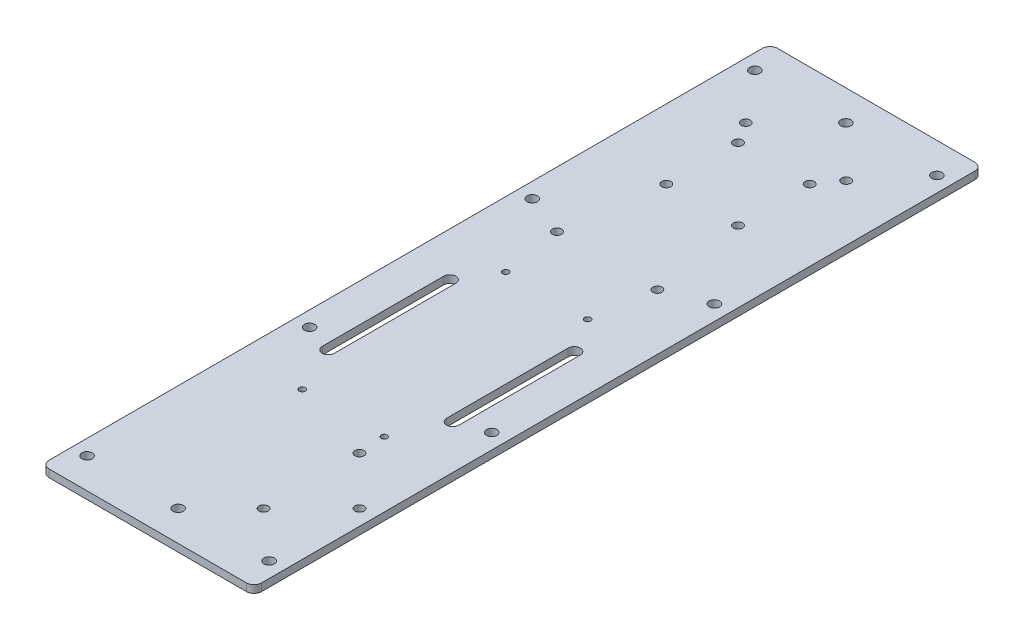
SolidWorks part; units mm, degrees
ref_plane "Front Plane" through (0, 0, 0) normal (0, 0, 1) x (1, 0, 0)
ref_plane "Top Plane" through (0, 0, 0) normal (0, 1, 0) x (1, 0, 0)
ref_plane "Right Plane" through (0, 0, 0) normal (1, 0, 0) x (0, 0, -1)
sketch "Sketch2" plane through (0, 0, 0) normal (0, 1, 0) x (1, 0, 0)
  line L0 (-44.45, 0) -> (44.45, 0) construction
  line L1 (-41.275, 152.4) -> (41.275, 152.4)
  line L2 (-44.45, 149.225) -> (-44.45, -149.225)
  line L3 (-41.275, -152.4) -> (41.275, -152.4)
  line L4 (44.45, 149.225) -> (44.45, -149.225)
  line L5 (0, 152.4) -> (0, -152.4) construction
  arc A0 (-44.45, -149.225) -> (-41.275, -152.4) centre (-41.275, -149.225) ccw
  arc A1 (41.275, -152.4) -> (44.45, -149.225) centre (41.275, -149.225) ccw
  arc A2 (41.275, 152.4) -> (44.45, 149.225) centre (41.275, 149.225) cw
  arc A3 (-41.275, 152.4) -> (-44.45, 149.225) centre (-41.275, 149.225) ccw
  point P8 (0, 0)
  point P13 (-44.45, -152.4)
  point P16 (44.45, -152.4)
  point P21 (-44.45, 152.4)
  dimension "D3" = 3.175
  dimension "D1" = 304.8
  dimension "D2" = 88.9
extrude "Plate Thickness" add sketch "Sketch2" along normal blind 3.175 contours L2 A0 L3 A1 L4 A2 L1 A3
sketch "Sketch3" plane through (0, 3.175, 0) normal (0, 1, 0) x (1, 0, 0)
  line L0 (-44.45, 149.225) -> (-44.45, -149.225) construction
  line L1 (-41.275, 152.4) -> (41.275, 152.4) construction
  line L4 (0, 152.4) -> (0, -152.4) construction
  line L5 (-41.275, -152.4) -> (41.275, -152.4) construction
  line L6 (-41.275, -152.4) -> (41.275, -152.4) construction
  circle A0 centre (-38.1, 139.7) radius 2.159
  circle A1 centre (-38.1, 46.5667) radius 2.159
  circle A2 centre (-38.1, -46.5667) radius 2.159
  circle A3 centre (-38.1, -139.7) radius 2.159
  circle A4 centre (38.1, -139.7) radius 2.159
  circle A5 centre (38.1, -46.5667) radius 2.159
  circle A6 centre (38.1, 46.5667) radius 2.159
  circle A7 centre (38.1, 139.7) radius 2.159
  circle A8 centre (0, 139.7) radius 2.159
  circle A9 centre (0, -139.7) radius 2.159
  point P6 (0, 0)
  point P37 (0, 0)
  dimension "D1" = 4.318
  dimension "D4" = 4.318
  dimension "D2" = 6.35
  dimension "D3" = 12.7
  dimension "D5" = 12.7
  dimension "D6" = 12.7
  dimension "D7" = 93.1333
  dimension "D8" = 93.1333
extrude "Mounting holes" cut sketch "Sketch3" against normal through all
sketch "Sketch4" plane through (0, 3.175, 0) normal (0, 1, 0) x (1, 0, 0)
  line L0 (-21.0058, 39.8143) -> (21.0058, 39.8143) construction
  line L1 (0, 0) -> (0, 139.7) construction
  circle A0 centre (-21.0058, 118.8083) radius 1.905
  circle A1 centre (-21.0058, 39.8143) radius 1.905
  circle A2 centre (21.0058, 39.8143) radius 1.905
  circle A3 centre (21.0058, 118.8083) radius 1.905
  point P13 (0, 39.8143)
  point P17 (0, 69.85)
  point P18 (0, 69.85)
  dimension "D1" = 3.81
  dimension "D2" = 78.994
  dimension "D3" = 42.0116
extrude "Jetson Holes (w/o mount)" cut sketch "Sketch4" against normal through all
sketch "Sketch5" plane through (0, 3.175, 0) normal (0, 1, 0) x (1, 0, 0)
  circle A1 centre (-15.3784, 109.9339) radius 1.905
  circle A3 centre (14.619, 109.9339) radius 1.905
  circle A4 centre (14.619, 79.9365) radius 1.905
  circle A5 centre (-15.3784, 79.9365) radius 1.905
  dimension "D1" = 3.81
  dimension "D2" = 29.9974
  dimension "D3" = 29.9974
extrude "PDB holes" cut sketch "Sketch5" against normal through all
sketch "Sketch6" plane through (0, 3.175, 0) normal (0, 1, 0) x (1, 0, 0)
  circle A6 centre (37.9835, -101.7966) radius 1.905
  circle A7 centre (17.9175, -81.7306) radius 1.905
  circle A8 centre (17.9175, -121.8626) radius 1.905
  point P0 (17.9175, -121.8626)
  dimension "D5" = 3.81
  dimension "D6" = 40.132
  dimension "D7" = 20.066
  dimension "D8" = 20.066
extrude "Lidar Holes" cut sketch "Sketch6" against normal through all
sketch "Sketch7" plane through (0, 3.175, 0) normal (0, 1, 0) x (1, 0, 0)
  line L0 (0, 152.4) -> (0, -152.4) construction
  line L1 (-41.275, 152.4) -> (41.275, 152.4) construction
  line L2 (-41.275, -152.4) -> (41.275, -152.4) construction
  line L3 (17.145, 14.4893) -> (-17.145, 14.4893) construction
  circle A0 centre (-17.145, 14.4893) radius 1.27
  circle A1 centre (-17.145, -70.6007) radius 1.27
  circle A2 centre (17.145, -70.6007) radius 1.27
  circle A3 centre (17.145, 14.4893) radius 1.27
  point P14 (0, 14.4893)
  point P15 (17.145, -67.9359)
  point P16 (17.145, -72.2087)
  point P17 (17.145, -70.6007)
  dimension "D1" = 2.54
  dimension "D2" = 85.09
  dimension "D3" = 34.29
extrude "PixHawk Holes" cut sketch "Sketch7" against normal through all
sketch "Sketch8" plane through (0, 3.175, 0) normal (0, 1, 0) x (1, 0, 0)
  line L0 (0, 152.4) -> (0, -115.5095) construction
  line L1 (-41.275, 152.4) -> (41.275, 152.4) construction
  line L2 (-26.035, -0.006) -> (-26.035, -50.806) construction
  line L3 (-23.495, -0.006) -> (-23.495, -50.806)
  line L4 (-28.575, -0.006) -> (-28.575, -50.806)
  line L5 (26.035, -0.006) -> (26.035, -50.806) construction
  line L6 (23.495, -0.006) -> (23.495, -50.806)
  line L7 (28.575, -0.006) -> (28.575, -50.806)
  arc A0 (-23.495, -0.006) -> (-28.575, -0.006) centre (-26.035, -0.006) ccw
  arc A1 (-28.575, -50.806) -> (-23.495, -50.806) centre (-26.035, -50.806) ccw
  arc A2 (23.495, -0.006) -> (28.575, -0.006) centre (26.035, -0.006) cw
  arc A3 (28.575, -50.806) -> (23.495, -50.806) centre (26.035, -50.806) cw
  point P7 (-26.035, -25.406)
  point P14 (26.035, -25.406)
  dimension "D1" = 50.8
  dimension "D2" = 5.08
  dimension "D3" = 26.035
extrude "Battery Holes" cut sketch "Sketch8" against normal through all
